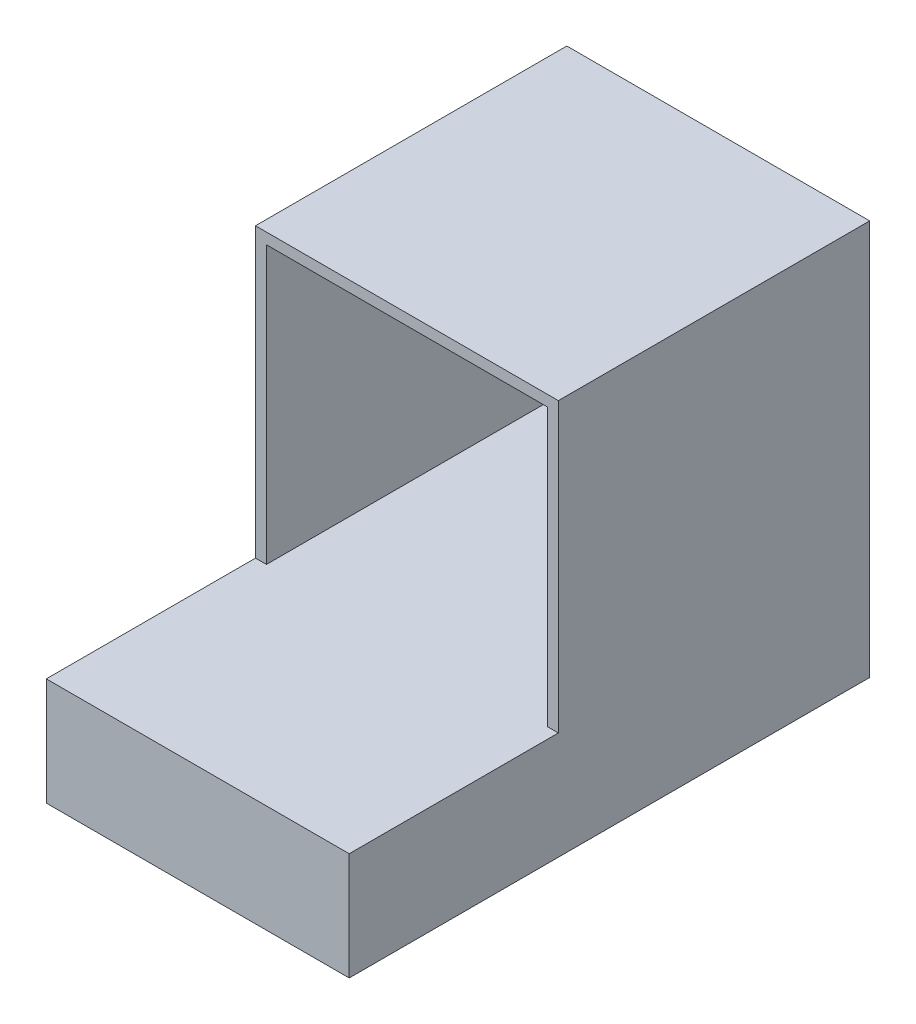
SolidWorks part; units mm, degrees
ref_plane "Front Plane" through (0, 0, 0) normal (0, 0, 1) x (1, 0, 0)
ref_plane "Top Plane" through (0, 0, 0) normal (0, 1, 0) x (1, 0, 0)
ref_plane "Right Plane" through (0, 0, 0) normal (1, 0, 0) x (0, 0, -1)
sketch "Sketch1" plane through (0, 0, 0) normal (0, 0, 1) x (1, 0, 0)
  line L1 (0, 0) -> (131.318, 0)
  line L2 (0, 0) -> (0, 171.45)
  line L3 (0, 171.45) -> (131.318, 171.45)
  line L4 (131.318, 0) -> (131.318, 171.45)
  dimension "D1" = 131.318
  dimension "D2" = 171.45
extrude "Boss-Extrude1" add sketch "Sketch1" along normal blind 134.9756
sketch "Sketch2" plane through (0, 0, 134.9756) normal (0, 0, 1) x (1, 0, 0)
  line L0 (131.318, 0) -> (131.318, 171.45) construction
  line L1 (0, 0) -> (131.318, 0)
  line L2 (0, 0) -> (0, 46.6598)
  line L3 (0, 46.6598) -> (131.318, 46.6598)
  line L4 (131.318, 0) -> (131.318, 46.6598)
  dimension "D1" = 46.6598
extrude "Boss-Extrude2" add sketch "Sketch2" along normal blind 90.678
shell "Shell1" thickness 4.7625 removed face at (65.659, 85.725, 0) removed face at (65.659, 109.0549, 134.9756)
sketch "Sketch3" plane through (0, 46.6598, 0) normal (0, 1, 0) x (1, 0, 0)
  line L0 (0, -134.9756) -> (0, 0) construction
  line L1 (131.318, -134.9756) -> (0, -134.9756)
  line L2 (131.318, -134.9756) -> (131.318, 0)
  line L3 (131.318, 0) -> (0, 0)
  line L4 (0, -134.9756) -> (0, 0)
  dimension "D1" = 134.9756
extrude "Boss-Extrude3" add sketch "Sketch3" against normal blind 4.7625
